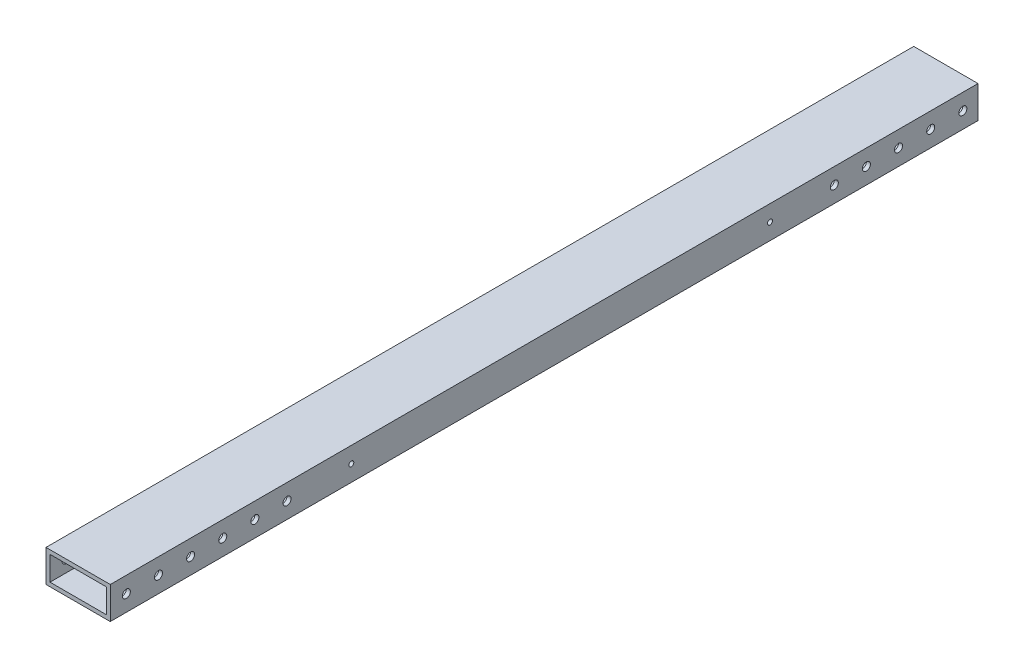
SolidWorks part; units mm, degrees
material "6061 Alloy"
ref_plane "Front Plane" through (0, 0, 0) normal (0, 0, 1) x (1, 0, 0)
ref_plane "Top Plane" through (0, 0, 0) normal (0, 1, 0) x (1, 0, 0)
ref_plane "Right Plane" through (0, 0, 0) normal (1, 0, 0) x (0, 0, -1)
sketch "Sketch1" plane through (0, 0, 0) normal (0, 0, 1) x (1, 0, 0)
  line L0 (-22.225, 9.525) -> (22.225, 9.525)
  line L2 (-25.4, 12.7) -> (25.4, 12.7)
  line L3 (-25.4, 12.7) -> (-25.4, -12.7)
  line L4 (-25.4, -12.7) -> (25.4, -12.7)
  line L5 (25.4, 12.7) -> (25.4, -12.7)
  line L10 (22.225, 9.525) -> (22.225, -9.525)
  line L11 (-22.225, -9.525) -> (22.225, -9.525)
  line L12 (-22.225, 9.525) -> (-22.225, -9.525)
  point P12 (0, 12.7)
  point P14 (25.4, 0)
  dimension "Wall Thickness" = 3.175
  dimension "Outside Width" = 50.8
  dimension "Outside Height" = 25.4
  dimension "Inside Height" = 19.05
  dimension "Inside Width" = 44.45
sketch "Sketch2" plane through (0, 0, 0) normal (1, 0, 0) x (0, 0, -1)
  line L0 (342.9, 0) -> (-342.9, 0)
  point P4 (0, 0)
  point P7 (-342.9, 0)
  point P10 (342.9, 0)
  dimension "Length" = 685.8
sketch "Sketch3" plane through (0, 0, 0) normal (0, 0, 1) x (1, 0, 0)
  line L21 (25.4, 12.7) -> (-25.4, 12.7)
  line L22 (25.4, -12.7) -> (25.4, 12.7)
  line L23 (-25.4, -12.7) -> (25.4, -12.7)
  line L24 (-25.4, 12.7) -> (-25.4, -12.7)
  line L25 (25.4, 12.7) -> (-25.4, 12.7)
  line L26 (25.4, -12.7) -> (25.4, 12.7)
  line L27 (-25.4, -12.7) -> (25.4, -12.7)
  line L28 (-25.4, 12.7) -> (-25.4, -12.7)
  line L29 (22.225, 9.525) -> (-22.225, 9.525)
  line L30 (22.225, -9.525) -> (22.225, 9.525)
  line L31 (-22.225, -9.525) -> (22.225, -9.525)
  line L32 (-22.225, 9.525) -> (-22.225, -9.525)
  line L33 (22.225, 9.525) -> (-22.225, 9.525)
  line L34 (22.225, -9.525) -> (22.225, 9.525)
  line L35 (-22.225, -9.525) -> (22.225, -9.525)
  line L36 (-22.225, 9.525) -> (-22.225, -9.525)
  dimension "D1" = 0
  dimension "D2" = 0
extrude "Boss-Extrude1" add sketch "Sketch3" along normal up to vertex (342.9 mm away) and the other way up to vertex (342.9 mm away) up to point (0, 0, 342.9) other way up to point (0, 0, -342.9)
sketch "Drawing Reference" plane through (0, 0, 0) normal (1, 0, 0) x (0, 0, -1)
  line L0 (-342.9, 0) -> (342.9, 0) construction
  line L1 (0, -12.7) -> (0, 12.7) construction
  line L2 (-342.9, -12.7) -> (342.9, -12.7) construction
  line L5 (-342.9, 12.7) -> (342.9, 12.7) construction
  point P7 (-306.324, 0)
  point P8 (306.324, 0)
  dimension "D1" = 36.576
sketch "Sketch5" plane through (25.4, 0, 0) normal (1, 0, 0) x (0, 0, -1)
  line L0 (-342.9, 0) -> (-279.4, 0)
  line L1 (-342.9, -12.7) -> (-342.9, 12.7) construction
  line L2 (-279.4, 0) -> (-254, 0)
  line L3 (-254, 0) -> (-228.6, 0)
  line L4 (-228.6, 0) -> (-203.2, 0)
sketch "Sketch8" plane through (25.4, 0, 0) normal (1, 0, 0) x (0, 0, -1)
  line L0 (342.9, 0) -> (305.5118, 0)
  line L1 (342.9, -12.7) -> (342.9, 12.7) construction
  line L2 (305.5118, 0) -> (280.1118, 0)
  line L3 (280.1118, 0) -> (254.7118, 0)
  line L4 (254.7118, 0) -> (229.3118, 0)
hole_wizard "1/4 (0.25) Diameter Hole3" positions "Sketch12" profile "Sketch13" hole size "1/4" standard "ANSI Inch" end condition through all
sketch "Sketch12" plane through (-25.4, 0, 0) normal (-1, 0, 0) x (0, 0, 1)
  point P0 (-330.9118, 0)
sketch "Sketch13" plane through (-25.4, 0, -330.9118) normal (0, 1, 0) x (0, 0, 1)
  line L0 (0, 0) -> (0, 50.8)
  line L1 (0, 50.8) -> (3.175, 50.8)
  line L2 (3.175, 50.8) -> (3.175, 0)
  line L5 (3.175, 0) -> (0, 0)
  line L11 (0, -6.35) -> (0, 107.95) construction
  dimension "Thru Hole Dia." = 6.35
  dimension "Thru Hole Depth" = 50.8
hole_wizard "1/4 (0.25) Diameter Hole4" positions "Sketch14" profile "Sketch15" hole size "1/4" standard "ANSI Inch" end condition through all
sketch "Sketch14" plane through (-25.4, 0, 0) normal (-1, 0, 0) x (0, 0, 1)
  point P0 (304.8, 0)
  point P3 (330.2, 0)
sketch "Sketch15" plane through (-25.4, 0, 304.8) normal (0, 1, 0) x (0, 0, 1)
  line L0 (0, 0) -> (0, 50.8)
  line L1 (0, 50.8) -> (3.175, 50.8)
  line L2 (3.175, 50.8) -> (3.175, 0)
  line L5 (3.175, 0) -> (0, 0)
  line L11 (0, -6.35) -> (0, 107.95) construction
  dimension "Thru Hole Dia." = 6.35
  dimension "Thru Hole Depth" = 50.8
hole_wizard "1/4 (0.25) Diameter Hole5" positions "Sketch17" profile "Sketch18" hole size "1/4" standard "ANSI Inch" end condition through all
sketch "Sketch17" plane through (25.4, 0, 0) normal (1, 0, 0) x (0, 0, -1)
  point P0 (305.5118, 0)
  point P3 (280.1118, 0)
sketch "Sketch18" plane through (25.4, 0, -305.5118) normal (0, 1, 0) x (0, 0, -1)
  line L0 (0, 0) -> (0, 50.8)
  line L1 (0, 50.8) -> (3.175, 50.8)
  line L2 (3.175, 50.8) -> (3.175, 0)
  line L5 (3.175, 0) -> (0, 0)
  line L11 (0, -6.35) -> (0, 107.95) construction
  dimension "Thru Hole Dia." = 6.35
  dimension "Thru Hole Depth" = 50.8
hole_wizard "1/4 (0.25) Diameter Hole6" positions "Sketch19" profile "Sketch20" hole size "1/4" standard "ANSI Inch" end condition through all
sketch "Sketch19" plane through (25.4, 0, 0) normal (1, 0, 0) x (0, 0, -1)
  point P0 (229.3118, 0)
  point P3 (254.7118, 0)
sketch "Sketch20" plane through (25.4, 0, -229.3118) normal (0, 1, 0) x (0, 0, -1)
  line L0 (0, 0) -> (0, 50.8)
  line L1 (0, 50.8) -> (3.175, 50.8)
  line L2 (3.175, 50.8) -> (3.175, 0)
  line L5 (3.175, 0) -> (0, 0)
  line L11 (0, -6.35) -> (0, 107.95) construction
  dimension "Thru Hole Dia." = 6.35
  dimension "Thru Hole Depth" = 50.8
hole_wizard "1/4 (0.25) Diameter Hole7" positions "Sketch21" profile "Sketch22" hole size "1/4" standard "ANSI Inch" end condition through all
sketch "Sketch21" plane through (25.4, 0, 0) normal (1, 0, 0) x (0, 0, -1)
  point P0 (-203.2, 0)
  point P3 (-228.6, 0)
sketch "Sketch22" plane through (25.4, 0, 203.2) normal (0, 1, 0) x (0, 0, -1)
  line L0 (0, 0) -> (0, 50.8)
  line L1 (0, 50.8) -> (3.175, 50.8)
  line L2 (3.175, 50.8) -> (3.175, 0)
  line L5 (3.175, 0) -> (0, 0)
  line L11 (0, -6.35) -> (0, 107.95) construction
  dimension "Thru Hole Dia." = 6.35
  dimension "Thru Hole Depth" = 50.8
hole_wizard "1/4 (0.25) Diameter Hole8" positions "Sketch23" profile "Sketch24" hole size "1/4" standard "ANSI Inch" end condition through all
sketch "Sketch23" plane through (25.4, 0, 0) normal (1, 0, 0) x (0, 0, -1)
  point P0 (-279.4, 0)
  point P3 (-254, 0)
sketch "Sketch24" plane through (25.4, 0, 279.4) normal (0, 1, 0) x (0, 0, -1)
  line L0 (0, 0) -> (0, 50.8)
  line L1 (0, 50.8) -> (3.175, 50.8)
  line L2 (3.175, 50.8) -> (3.175, 0)
  line L5 (3.175, 0) -> (0, 0)
  line L11 (0, -6.35) -> (0, 107.95) construction
  dimension "Thru Hole Dia." = 6.35
  dimension "Thru Hole Depth" = 50.8
sketch "Sketch25" plane through (25.4, 0, 0) normal (1, 0, 0) x (0, 0, -1)
  line L0 (-203.2, 0) -> (-152.4, 0)
  line L1 (229.3118, 0) -> (178.5118, 0)
hole_wizard "5/32 (0.15625) Diameter Hole1" positions "Sketch26" profile "Sketch27" hole size "5/32" standard "ANSI Inch" end condition through all
sketch "Sketch26" plane through (25.4, 0, 0) normal (1, 0, 0) x (0, 0, -1)
  point P0 (-152.4, 0)
  point P3 (178.5118, 0)
sketch "Sketch27" plane through (25.4, 0, 152.4) normal (0, 1, 0) x (0, 0, -1)
  line L0 (0, 0) -> (0, 50.8)
  line L1 (0, 50.8) -> (1.9844, 50.8)
  line L2 (1.9844, 50.8) -> (1.9844, 0)
  line L5 (1.9844, 0) -> (0, 0)
  line L11 (0, -6.35) -> (0, 107.95) construction
  dimension "Thru Hole Dia." = 3.9688
  dimension "Thru Hole Depth" = 50.8
sketch "Sketch30" plane through (-25.4, 0, 0) normal (-1, 0, 0) x (0, 0, 1)
  point P0 (-128.9434, 0.355)
  point P1 (-103.5434, 0.3445)
  point P2 (77.4316, 0.355)
  point P3 (102.8316, 0.355)
hole_wizard "1/2 (0.5) Diameter Hole1" positions "Sketch33" profile "Sketch34" hole size "1/2" standard "ANSI Inch"
sketch "Sketch33" plane through (-25.4, 0, 0) normal (-1, 0, 0) x (0, 0, 1)
  point P0 (-128.9434, 0.355)
  point P3 (-103.5434, 0.3445)
  point P7 (77.4316, 0.355)
  point P10 (102.8316, 0.355)
sketch "Sketch34" plane through (-25.4, 0.355, -128.9434) normal (0, 1, 0) x (0, 0, 1)
  line L0 (0, 0) -> (0, 10.1655)
  line L1 (0, 10.1655) -> (6.35, 6.35)
  line L2 (6.35, 6.35) -> (6.35, 0)
  line L5 (6.35, 0) -> (0, 0)
  line L10 (0, 10.1655) -> (-6.35, 6.35) construction
  line L11 (0, -6.35) -> (0, 107.95) construction
  dimension "Hole Dia." = 12.7
  dimension "Hole Depth" = 6.35
  dimension "Drill Angle" = 118
equation "\"D1@Drawing Reference\"=\"Outside Width@Sketch1\" * 0.72"
